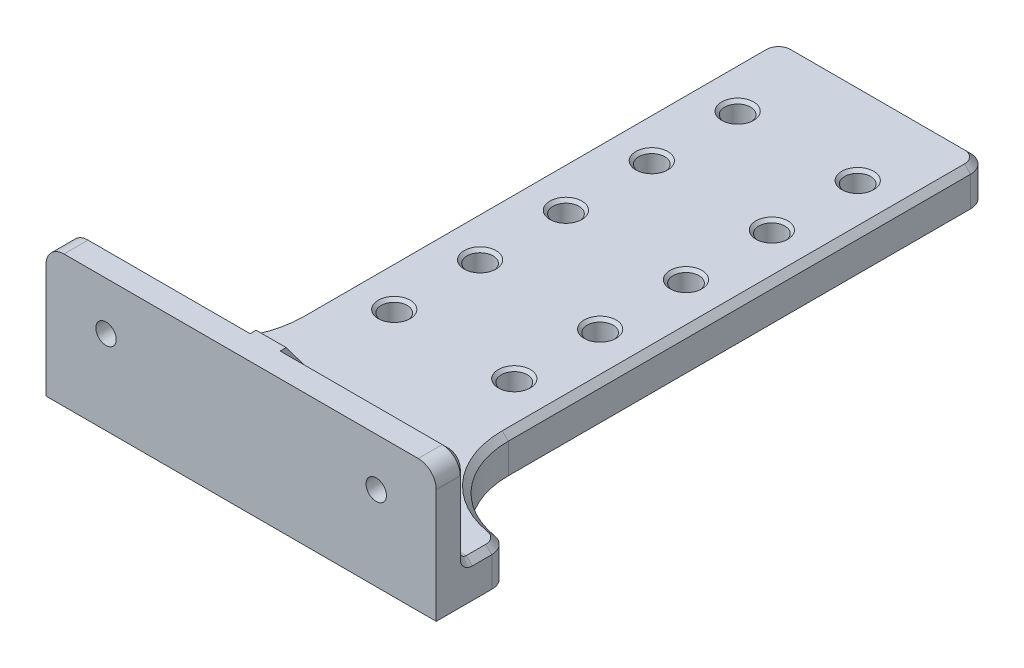
SolidWorks part; units mm, degrees
material "ABS"
ref_plane "Front Plane" through (0, 0, 0) normal (0, 0, 1) x (1, 0, 0)
ref_plane "Top Plane" through (0, 0, 0) normal (0, 1, 0) x (1, 0, 0)
ref_plane "Right Plane" through (0, 0, 0) normal (1, 0, 0) x (0, 0, -1)
sketch "Sketch1" plane through (0, 0, 0) normal (1, 0, 0) x (0, 0, -1)
  line L1 (0, 0) -> (-5, 0)
  line L2 (0, 0) -> (0, 22)
  line L3 (0, 22) -> (-5, 22)
  line L4 (-5, 0) -> (-5, 22)
  dimension "D1" = 5
  dimension "D2" = 22
extrude "Boss-Extrude1" add sketch "Sketch1" along normal blind 65
sketch "Sketch2" plane through (0, 0, 0) normal (0, 1, 0) x (1, 0, 0)
  line L0 (65, 0) -> (0, 0) construction
  line L1 (50, 0) -> (15, 0)
  line L2 (50, 0) -> (50, 102)
  line L3 (50, 102) -> (15, 102)
  line L4 (15, 0) -> (15, 102)
  line L5 (32.5, 102) -> (32.5, 0) construction
  line L7 (0, 0) -> (65, 0)
  line L8 (0, 0) -> (0, 7)
  line L9 (0, 7) -> (65, 7)
  line L10 (65, 0) -> (65, 7)
  dimension "D1" = 102
  dimension "D2" = 35
  dimension "D3" = 7
extrude "Boss-Extrude2" add sketch "Sketch2" along normal blind 6 contours L5 L3 L4 L9 | L3 L5 L9 L2 | L9 L5 L1 L2 | L5 L9 L4 L7 | L9 L8 L7 L4 | L7 L10 L9 L2 region at (41.25, 0, -3.5) region at (57.5, 0, -3.5) region at (23.75, 0, -3.5) region at (41.25, 0, -54.5) region at (7.5, 0, -3.5) region at (23.75, 0, -54.5)
sketch "Sketch3" plane through (0, 0, 0) normal (0, 0, -1) x (-1, 0, 0)
  line L5 (-55, 14) -> (-65, 14) construction
  line L6 (-65, 6) -> (-65, 22) construction
  line L8 (0, 14) -> (-10, 14) construction
  line L9 (0, 6) -> (0, 22) construction
  point P0 (-55, 14)
  point P2 (-10, 14)
  dimension "D1" = 45
hole_wizard "CSK for M3 Flat Head Machine Screw1" positions "Sketch3" profile "Sketch4" countersink size "M3" standard "ANSI Metric" end condition up to next
sketch "Sketch4" plane through (55, 14, 0) normal (1, 0, 0) x (0, 1, 0)
  line L0 (0, 0) -> (0, 5)
  line L1 (0, 5) -> (1.7, 5)
  line L2 (1.7, 5) -> (1.7, 1.45)
  line L3 (1.7, 1.45) -> (3.15, 0)
  line L5 (3.15, 0) -> (0, 0)
  line L6 (-1.7, 1.45) -> (-3.15, 0) construction
  line L11 (0, -6.35) -> (0, 107.95) construction
  dimension "Thru Hole Dia." = 3.4
  dimension "Thru Hole Depth" = 5
  dimension "Near C'Sink Dia." = 6.3
  dimension "Near C'Sink Angle" = 90
sketch "Sketch6" plane through (0, 6, 0) normal (0, 1, 0) x (1, 0, 0)
  line L0 (32.5, 102) -> (32.5, 0) construction
  line L2 (65, 0) -> (0, 0) construction
  line L4 (22.5, 30.5) -> (42.5, 30.5) construction
  line L6 (22.5, 44.8) -> (42.5, 44.8) construction
  line L8 (42.5, 59.1) -> (22.5, 59.1) construction
  line L10 (22.5, 73.4) -> (42.5, 73.4) construction
  line L11 (22.5, 30.5) -> (22.5, 44.8) construction
  line L12 (22.5, 44.8) -> (22.5, 59.1) construction
  line L13 (22.5, 59.1) -> (22.5, 73.4) construction
  line L15 (22.5, 30.5) -> (22.5, 0) construction
  line L19 (22.5, 87.7) -> (42.5, 87.7) construction
  line L20 (22.5, 73.4) -> (22.5, 87.7) construction
  line L23 (22.5, 87.7) -> (22.5, 102) construction
  line L26 (65, 0) -> (0, 0) construction
  line L27 (50, 102) -> (15, 102) construction
  point P0 (22.5, 30.5)
  point P2 (42.5, 30.5)
  point P4 (42.5, 44.8)
  point P6 (22.5, 44.8)
  point P8 (22.5, 59.1)
  point P10 (42.5, 59.1)
  point P12 (42.5, 73.4)
  point P14 (22.5, 73.4)
  point P61 (32.5, 59.1)
  point P63 (32.5, 73.4)
  point P64 (32.5, 44.8)
  point P92 (32.5, 87.7)
  point P95 (22.5, 87.7)
  point P98 (42.5, 87.7)
  dimension "D1" = 20
  dimension "D2" = 30.5
hole_wizard "M3 Clearance Hole2" positions "Sketch6" profile "Sketch7" hole size "M3" standard "ANSI Metric" end condition up to next
sketch "Sketch7" plane through (22.5, 6, -30.5) normal (1, 0, 0) x (0, 0, 1)
  line L0 (0, 0) -> (0, 6)
  line L1 (0, 6) -> (2.2, 6)
  line L2 (1.7, 5.5) -> (1.7, 0)
  line L5 (1.7, 0) -> (0, 0)
  line L7 (2.2, 6) -> (1.7, 5.5)
  line L8 (-2.2, 6) -> (-1.7, 5.5) construction
  line L11 (0, -6.35) -> (0, 107.95) construction
  dimension "Thru Hole Dia." = 3.4
  dimension "Thru Hole Depth" = 6
  dimension "Far C'Sink Dia." = 4.4
  dimension "Far C'Sink Angle" = 90
sketch "Sketch8" plane through (0, 6, 0) normal (0, 1, 0) x (1, 0, 0)
  circle A0 centre (22.5, 87.7) radius 2.165
  circle A1 centre (42.5, 87.7) radius 2.165
  circle A2 centre (22.5, 73.4) radius 2.165
  circle A3 centre (42.5, 73.4) radius 2.165
  circle A4 centre (22.5, 59.1) radius 2.165
  circle A5 centre (42.5, 59.1) radius 2.165
  circle A6 centre (22.5, 44.8) radius 2.165
  circle A7 centre (42.5, 44.8) radius 2.165
  circle A8 centre (22.5, 30.5) radius 2.165
  circle A9 centre (42.5, 30.5) radius 2.165
  dimension "D1" = 4.33
extrude "Cut-Extrude1" cut sketch "Sketch8" against normal blind 5
ref_plane "Plane1" through (32.5, 0, 0) normal (1, 0, 0) x (0, 0, -1)
sketch "Sketch9" plane through (32.5, 0, 0) normal (1, 0, 0) x (0, 0, -1)
  line L1 (0, 22) -> (12, 6)
  line L4 (61.265, 6) -> (56.935, 6) construction
  dimension "D1" = 20
rib "Rib5" sketch "Sketch9" sketch "Sketch9" thickness 5 extrusion direction parallel to sketch draft on no parameters "D1"=5
fillet "Fillet1" radius 15 2 edges at (50, 3, -7) (15, 3, -7)
fillet "Fillet2" radius 3 6 edges at (50, 3, -102) (15, 3, -102) (65, 22, 2.5) (0, 22, 2.5) (0, 3, -7) (65, 3, -7)
fillet "Fillet6" radius 1 5 edges at (32.5, 6, -12) (35, 6, -6) (30, 6, -6) (15, 6, 0) (50, 6, 0)
chamfer "Chamfer1" distance 1 angle 45 19 edges at (0, 6, -2.6259) (65, 6, -2.6259) (11.4564, 6, -12.3175) (15, 6, -60.5) (15.8787, 6, -101.1213) (32.5, 6, -102) (53.5436, 6, -12.3175) (49.1213, 6, -101.1213) (50, 6, -60.5) (0.7087, 6, -6.1883) (64.2913, 6, -6.1883) (65, 13, 0) (64.1213, 21.1213, 0) (48.5, 22, 0) (0, 13, 0) (0.8787, 21.1213, 0) (16.5, 22, 0) (0, 6.2929, -0.2929) (65, 6.2929, -0.2929)
chamfer "Chamfer2" distance 0.5 angle 45 10 edges at (22.5, 6, -85.535) (22.5, 6, -71.235) (22.5, 6, -56.935) (22.5, 6, -42.635) (22.5, 6, -28.335) (42.5, 6, -28.335) (42.5, 6, -42.635) (42.5, 6, -56.935) (42.5, 6, -71.235) (42.5, 6, -85.535)
